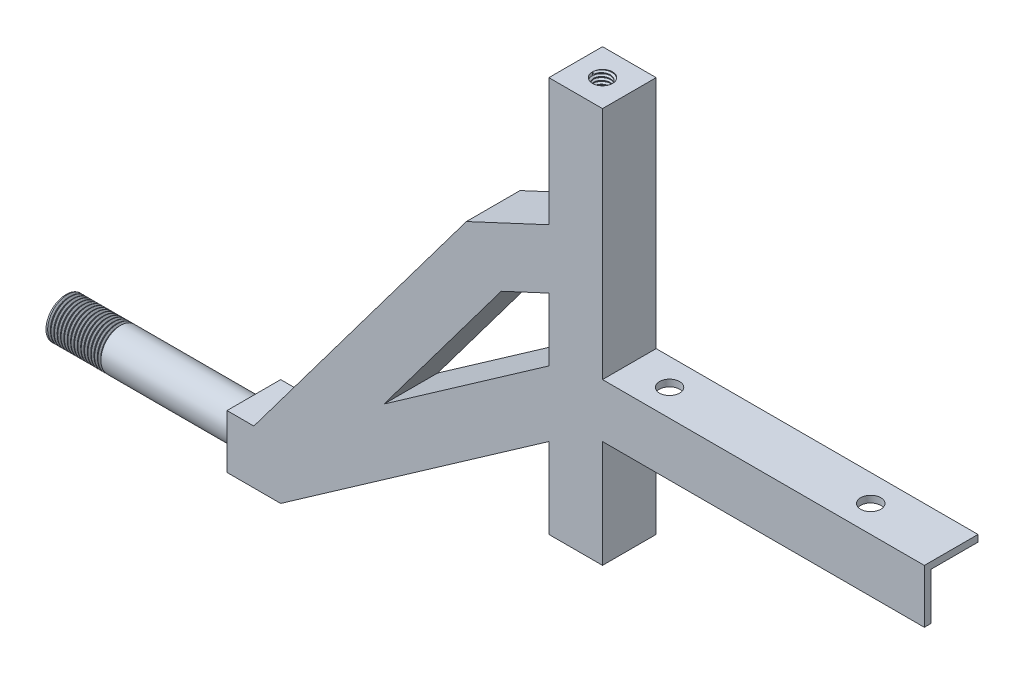
SolidWorks part; units mm, degrees
material "Plain Carbon Steel"
ref_plane "Front Plane" through (0, 0, 0) normal (0, 0, 1) x (1, 0, 0)
ref_plane "Top Plane" through (0, 0, 0) normal (0, 1, 0) x (1, 0, 0)
ref_plane "Right Plane" through (0, 0, 0) normal (1, 0, 0) x (0, 0, -1)
sketch "Sketch1" plane through (0, 0, 0) normal (0, 1, 0) x (1, 0, 0)
  line L1 (12.7, -12.7) -> (-12.7, -12.7)
  line L2 (12.7, -12.7) -> (12.7, 12.7)
  line L3 (12.7, 12.7) -> (-12.7, 12.7)
  line L4 (-12.7, -12.7) -> (-12.7, 12.7)
  line L5 (12.7, -12.7) -> (-12.7, 12.7) construction
  line L6 (12.7, 12.7) -> (-12.7, -12.7) construction
  line L7 (10.16, -10.16) -> (-10.16, -10.16)
  line L8 (10.16, -10.16) -> (10.16, 10.16)
  line L9 (10.16, 10.16) -> (-10.16, 10.16)
  line L10 (-10.16, -10.16) -> (-10.16, 10.16)
  line L11 (10.16, -10.16) -> (-10.16, 10.16) construction
  line L12 (10.16, 10.16) -> (-10.16, -10.16) construction
  point P0 (0, 0)
  point P5 (0, 0)
  dimension "D1" = 2.54
  dimension "1" = 25.4
extrude "Sq_Tb Extrude" add sketch "Sketch1" along normal blind 187.325
sketch "Sketch3" plane through (0, 187.325, 0) normal (0, 1, 0) x (1, 0, 0)
  line L1 (10.16, -10.16) -> (-10.16, -10.16)
  line L2 (10.16, -10.16) -> (10.16, 10.16)
  line L3 (10.16, 10.16) -> (-10.16, 10.16)
  line L4 (-10.16, -10.16) -> (-10.16, 10.16)
  line L5 (10.16, -10.16) -> (-10.16, 10.16) construction
  line L6 (10.16, 10.16) -> (-10.16, -10.16) construction
  circle A0 centre (0, 0) radius 4.7625
  point P0 (0, 0)
  dimension "D1" = 9.525
extrude "End Caps" add sketch "Sketch3" against normal blind 6.35
ref_plane "Mid-Plane" through (0, 93.6625, 0) normal (0, 1, 0) x (1, 0, 0)
mirror "End Cap Mirror" about plane through (0, 93.6625, 0) normal (0, 1, 0) of "End Caps"
thread "Top Thread" pitch 1.5875 method extrude profile "Thread Profile1" start angle 0, offset 0, length 0, pitch 1.5875, diameter 9.525
ref_plane "Plane2" through (-4.7625, 187.325, 0) normal (0, 0, 1) x (-1, 0, 0)
sketch "Thread Profile1" plane through (-4.7625, 187.325, 0) normal (0, 0, 1) x (-1, 0, 0)
  line L0 (0, 0) -> (0, 1.5875) construction
  line L11 (0, 0) -> (0, 1.3891)
  line L12 (0, 1.3891) -> (-0.8593, 0.893)
  line L13 (-0.8593, 0.893) -> (-0.8593, 0.4961)
  line L15 (-0.8593, 0.4961) -> (0, 0)
  line L17 (-0.8593, 0.6945) -> (0, 0.6945) construction
  point P2 (0, 0)
  dimension "Pitch" = 1.5875
  dimension "Profile_Angle" = 60
  dimension "Profile_Land" = 0.3969
  dimension "Profile_Height" = 0.8593
thread "Bottom Thread" pitch 1.5875 method extrude profile "Thread Profile2" start angle 0, offset 0, length 0, pitch 1.5875, diameter 9.525
ref_plane "Plane3" through (4.7625, 0, 0) normal (0, 0, 1) x (1, 0, 0)
sketch "Thread Profile2" plane through (4.7625, 0, 0) normal (0, 0, 1) x (1, 0, 0)
  line L0 (0, 0) -> (0, 1.5875) construction
  line L11 (0, 0) -> (0, 1.3891)
  line L12 (0, 1.3891) -> (-0.8593, 0.893)
  line L13 (-0.8593, 0.893) -> (-0.8593, 0.4961)
  line L15 (-0.8593, 0.4961) -> (0, 0)
  line L17 (-0.8593, 0.6945) -> (0, 0.6945) construction
  point P2 (0, 0)
  dimension "Pitch" = 1.5875
  dimension "Profile_Angle" = 60
  dimension "Profile_Land" = 0.3969
  dimension "Profile_Height" = 0.8593
sketch "Sketch9" plane through (0, 0, 0) normal (0, 0, 1) x (1, 0, 0)
  line L0 (-12.7, 126.996) -> (-51.7653, 108.7796)
  line L1 (-12.7, 187.325) -> (-12.7, 0) construction
  line L2 (-102.0827, 41.6898) -> (-81.7627, 26.4498) construction
  line L3 (-35.2635, 88.4487) -> (-12.7, 98.9702)
  line L4 (-12.7, 38.0909) -> (-139.7, -50.8)
  line L5 (-90.7525, 14.4633) -> (-12.7, 69.0945)
  line L6 (-12.7, 69.0945) -> (-12.7, 38.0909)
  line L8 (-51.7653, 108.7796) -> (-152.4, -25.4)
  line L9 (-12.7, 126.996) -> (-12.7, 98.9702)
  line L10 (-139.7, -50.8) -> (-35.2635, 88.4487)
  line L11 (-139.7, -50.8) -> (-165.1, -50.8)
  line L12 (-165.1, -50.8) -> (-165.1, -25.4)
  line L13 (-165.1, -25.4) -> (-152.4, -25.4)
  line L14 (-32.2327, 117.8878) -> (-21.4982, 94.8676) construction
  line L15 (-165.1, -38.1) -> (0, -38.1) construction
  line L16 (0, -38.1) -> (0, 0) construction
  line L18 (-12.7, 0) -> (12.7, 0) construction
  line L19 (-51.7262, 41.7789) -> (-37.1613, 20.9697) construction
  line L20 (-12.7, 69.0945) -> (32.9312, 3.9003) construction
  line L21 (-139.7, -50.8) -> (-114.9192, -86.2048) construction
  dimension "D3" = 172.7962
  dimension "D1" = 25.4
  dimension "D2" = 43.1038
  dimension "D4" = 65
  dimension "D5" = 12.7
  dimension "D6" = 152.4
  dimension "D7" = 115
  dimension "D8" = 25.4
  dimension "D9" = 50.8
  dimension "D10" = 55.011
  dimension "D11" = 60.329
  dimension "D12" = 38.0909
  dimension "D13" = 88.9052
extrude "Sq_Tb Angles" add sketch "Sketch9" along normal blind 12.7 and the other way blind 12.7 contours L13 L12 L11 L10 L3 L9 L0 L8 | L10 L4 L6 L5 region at (-89.8222, 35.9011, 0) region at (-64.9368, 15.7972, 0)
sketch "Sketch11" plane through (0, 0, 0) normal (0, 0, 1) x (1, 0, 0)
  line L0 (-165.1, -38.1) -> (-254, -38.1)
  line L1 (-165.1, -50.8) -> (-165.1, -25.4) construction
  line L2 (-254, -38.1) -> (-254, -28.575)
  line L3 (-254, -28.575) -> (-165.1, -28.575)
  line L6 (-165.1, -28.575) -> (-165.1, -38.1)
  dimension "D2" = 9.525
  dimension "D4" = 88.9
revolve "Wheel Rod" add sketch "Sketch11" angle 360 about L0
thread "Wheel Threads" pitch 1.5875 method cut profile "Thread Profile3" start angle 0, offset 0, length 25.4, pitch 1.5875, diameter 19.05
ref_plane "Plane4" through (-254, -38.1, -9.525) normal (0, -1, 0) x (0, 0, -1)
sketch "Thread Profile3" plane through (-254, -38.1, -9.525) normal (0, -1, 0) x (0, 0, -1)
  line L0 (0, 0) -> (0, 1.5875) construction
  line L11 (0, 0) -> (0, 1.3891)
  line L12 (0, 1.3891) -> (-0.8593, 0.893)
  line L13 (-0.8593, 0.893) -> (-0.8593, 0.4961)
  line L15 (-0.8593, 0.4961) -> (0, 0)
  line L17 (-0.8593, 0.6945) -> (0, 0.6945) construction
  point P2 (0, 0)
  dimension "Pitch" = 1.5875
  dimension "Profile_Angle" = 60
  dimension "Profile_Land" = 0.3969
  dimension "Profile_Height" = 0.8593
ref_plane "Tie-Rod Mount Plane" through (0, 34.925, 0) normal (0, 1, 0) x (1, 0, 0)
sketch "Sketch15" plane through (0, 34.925, 0) normal (0, 1, 0) x (1, 0, 0)
  line L0 (0, 12.7) -> (12.7, 25.4)
  line L1 (12.7, 12.7) -> (-12.7, 12.7) construction
  line L2 (12.7, 25.4) -> (76.2, 25.4)
  line L3 (0, -12.7) -> (12.7, -25.4)
  line L4 (-12.7, -12.7) -> (12.7, -12.7) construction
  line L5 (0, 12.7) -> (12.7, 12.7)
  line L6 (12.7, -12.7) -> (12.7, 12.7) construction
  line L7 (12.7, 12.7) -> (12.7, -12.7)
  line L8 (12.7, -12.7) -> (0, -12.7)
  line L9 (12.7, -25.4) -> (76.2, -25.4)
  line L10 (76.2, -25.4) -> (76.2, 25.4) construction
  line L11 (12.7, 25.4) -> (12.7, 12.7) construction
  line L12 (12.7, -12.7) -> (12.7, -25.4) construction
  line L13 (76.2, 25.4) -> (88.9, 12.7)
  line L14 (88.9, 12.7) -> (88.9, -12.7)
  line L15 (88.9, -12.7) -> (76.2, -25.4)
  line L16 (12.7, 0) -> (88.9, 0) construction
  dimension "D1" = 12.7
  dimension "D2" = 76.2
  dimension "D3" = 12.7
extrude "Tie-Rod Mount Plate" [suppressed] add sketch "Sketch15" along normal blind 6.35
sketch "Sketch16" [suppressed] plane through (0, 41.275, 0) normal (0, 1, 0) x (1, 0, 0)
  line L0 (12.7, 0) -> (63.5, 0) construction
  line L1 (12.7, -12.7) -> (12.7, 12.7) construction
  line L2 (63.5, 0) -> (63.5, 15.875) construction
  line L3 (12.7, 0) -> (76.2, 0) construction
  circle A0 centre (63.5, 15.875) radius 4.7625
  circle A1 centre (63.5, -15.875) radius 4.7625
  circle A2 centre (76.2, 0) radius 4.7625
  dimension "D1" = 50.8
  dimension "D3" = 9.525
  dimension "D2" = 15.875
  dimension "D4" = 63.5
extrude "Tie-Rod Mount Hole" [suppressed] cut sketch "Sketch16" against normal through all
ref_plane "Plane5" through (0, 50.8, 0) normal (0, -1, 0) x (-1, 0, 0)
sketch "Sketch17" plane through (0, 50.8, 0) normal (0, -1, 0) x (-1, 0, 0)
  line L0 (-12.7, -12.7) -> (-12.7, 12.7) construction
  line L1 (-12.7, 12.7) -> (12.7, 12.7)
  line L2 (-12.7, 12.7) -> (-12.7, 88.9)
  line L3 (-12.7, 88.9) -> (12.7, 88.9)
  line L4 (12.7, 12.7) -> (12.7, 88.9)
  line L5 (-12.7, 12.7) -> (12.7, 88.9) construction
  line L6 (-12.7, 88.9) -> (12.7, 12.7) construction
  line L7 (-12.7, 12.7) -> (12.7, 12.7) construction
  point P4 (0, 50.8)
  dimension "D1" = 25.4
  dimension "D2" = 76.2
extrude "Boss-Extrude1" [suppressed] add sketch "Sketch17" against normal blind 25.4
sketch "Sketch18" [suppressed] plane through (0, 76.2, 0) normal (0, 1, 0) x (1, 0, 0)
  line L0 (0, 0) -> (0, 63.5) construction
  circle A0 centre (0, 63.5) radius 4.7625
  dimension "D1" = 63.5
  dimension "D2" = 9.525
extrude "Cut-Extrude1" [suppressed] cut sketch "Sketch18" against normal through all
sketch "Sketch19" plane through (12.7, 0, 0) normal (1, 0, 0) x (0, 0, -1)
  line L0 (12.7, 76.2) -> (-12.7, 76.2)
  line L1 (-12.7, 187.325) -> (-12.7, 0) construction
  line L2 (-12.7, 76.2) -> (-12.7, 50.8)
  line L3 (-65.0506, 50.8) -> (65.0506, 50.8) construction
  line L4 (-12.7, 50.8) -> (-9.525, 50.8)
  line L5 (-9.525, 50.8) -> (-9.525, 73.025)
  line L6 (-9.525, 73.025) -> (12.7, 73.025)
  line L7 (12.7, 73.025) -> (12.7, 76.2)
  line L8 (-12.7, 0) -> (12.7, 0) construction
  point P10 (0, 0)
  dimension "D1" = 3.175
  dimension "D2" = 76.2
extrude "Boss-Extrude2" add sketch "Sketch19" along normal blind 152.4
sketch "Sketch20" plane through (0, 76.2, 0) normal (0, 1, 0) x (1, 0, 0)
  line L0 (88.9, -12.7) -> (88.9, 0) construction
  line L2 (165.1, -12.7) -> (12.7, -12.7) construction
  line L3 (0, 0) -> (31.75, 0) construction
  line L4 (31.75, 0) -> (127, 0) construction
  circle A0 centre (127, 0) radius 4.7625
  circle A1 centre (31.75, 0) radius 4.7625
  point P8 (88.9, 0)
  dimension "D1" = 31.75
  dimension "D2" = 9.525
  dimension "D3" = 127
extrude "Cut-Extrude2" cut sketch "Sketch20" against normal through all
